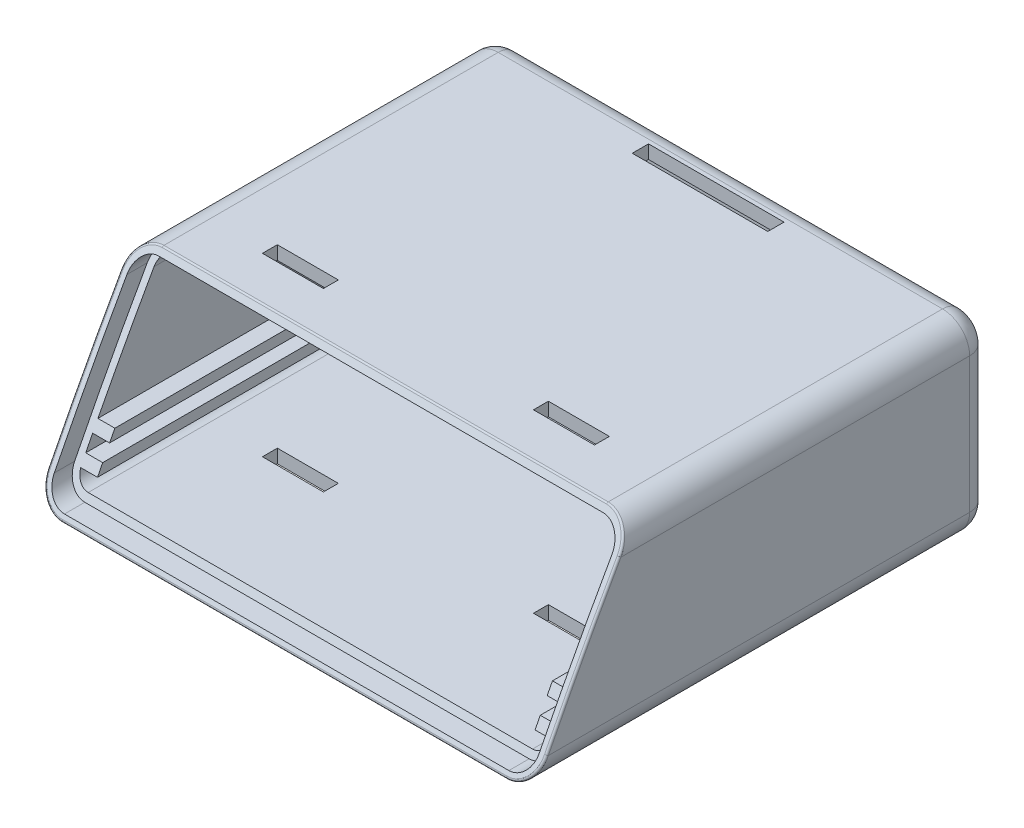
SolidWorks part; units mm, degrees
ref_plane "Front Plane" through (0, 0, 0) normal (0, 0, 1) x (1, 0, 0)
ref_plane "Top Plane" through (0, 0, 0) normal (0, 1, 0) x (1, 0, 0)
ref_plane "Right Plane" through (0, 0, 0) normal (1, 0, 0) x (0, 0, -1)
sketch "Sketch1" plane through (0, 0, 0) normal (0, 1, 0) x (1, 0, 0)
  line L1 (-36.79, -33.75) -> (36.79, -33.75)
  line L2 (-36.79, -33.75) -> (-36.79, 33.75)
  line L3 (-36.79, 33.75) -> (36.79, 33.75)
  line L4 (36.79, -33.75) -> (36.79, 33.75)
  line L5 (-36.79, -33.75) -> (36.79, 33.75) construction
  line L6 (-36.79, 33.75) -> (36.79, -33.75) construction
  point P0 (0, 0)
  dimension "D1" = 67.5
  dimension "D2" = 73.58
extrude "Boss-Extrude1" add sketch "Sketch1" along normal blind 28
fillet "Fillet1" radius 4 4 edges at (36.79, 28, 0) (36.79, 0, 0) (-36.79, 0, 0) (-36.79, 28, 0)
shell "Shell1" thickness 2
sketch "Sketch2" plane through (-36.79, 0, 0) normal (-1, 0, 0) x (0, 0, 1)
  line L0 (-33.75, 28) -> (33.75, 28) construction
  line L1 (18.75, 28) -> (33.75, 28)
  line L2 (33.75, 28) -> (33.75, 0)
  arc A0 (33.75, 0) -> (18.75, 28) centre (-392.2189, -210.1797) ccw
  dimension "D1" = 15
  dimension "D2" = 475
extrude "Cut-Extrude1" cut sketch "Sketch2" against normal through all
sketch "Sketch3" plane through (0, 0, -33.75) normal (0, 0, -1) x (-1, 0, 0)
  line L0 (-7.15, 18.7) -> (7.15, 18.7)
  line L1 (-6.95, 18.5) -> (6.95, 18.5) construction
  line L2 (-6.95, 18.5) -> (-6.95, 2.2) construction
  line L3 (-6.95, 2.2) -> (6.95, 2.2) construction
  line L4 (6.95, 18.5) -> (6.95, 2.2) construction
  line L5 (7.15, 18.7) -> (7.15, 2)
  line L6 (-7.15, 2) -> (7.15, 2)
  line L7 (-7.15, 18.7) -> (-7.15, 2)
  line L8 (27.25, 17.2) -> (38.3, 17.2)
  line L9 (27.45, 17) -> (38.1, 17) construction
  line L10 (27.45, 17) -> (27.45, 3.35) construction
  line L11 (27.45, 3.35) -> (38.1, 3.35) construction
  line L12 (38.1, 17) -> (38.1, 3.35) construction
  line L13 (38.3, 17.2) -> (38.3, 3.15)
  line L14 (27.25, 3.15) -> (38.3, 3.15)
  line L15 (27.25, 17.2) -> (27.25, 3.15)
  dimension "D1" = 0.2
  dimension "D2" = 0.2
fillet "Fillet2" radius 3 8 edges at (35.6184, 26.8284, -33.75) (36.79, 14, -33.75) (35.6184, 1.1716, -33.75) (0, 0, -33.75) (-35.6184, 1.1716, -33.75) (-36.79, 14, -33.75) (-35.6184, 26.8284, -33.75) (0, 28, -33.75)
sketch "Sketch4" plane through (0, 0, -31.75) normal (0, 0, 1) x (1, 0, 0)
  line L0 (32.79, 27) -> (-32.79, 27)
  line L1 (-35.79, 24) -> (-35.79, 4)
  line L2 (-32.79, 1) -> (32.79, 1)
  line L3 (35.79, 4) -> (35.79, 24)
  line L4 (32.79, 26) -> (-32.79, 26)
  line L5 (-34.79, 24) -> (-34.79, 4)
  line L6 (-32.79, 2) -> (32.79, 2)
  line L7 (34.79, 4) -> (34.79, 24)
  line L8 (32.79, 26) -> (-32.79, 26)
  line L9 (-34.79, 24) -> (-34.79, 4)
  line L10 (-32.79, 2) -> (32.79, 2)
  line L11 (34.79, 4) -> (34.79, 24)
  arc A0 (-32.79, 27) -> (-35.79, 24) centre (-32.79, 24) ccw
  arc A1 (-35.79, 4) -> (-32.79, 1) centre (-32.79, 4) ccw
  arc A2 (32.79, 1) -> (35.79, 4) centre (32.79, 4) ccw
  arc A3 (35.79, 24) -> (32.79, 27) centre (32.79, 24) ccw
  arc A4 (-32.79, 26) -> (-34.79, 24) centre (-32.79, 24) ccw
  arc A5 (-34.79, 4) -> (-32.79, 2) centre (-32.79, 4) ccw
  arc A6 (32.79, 2) -> (34.79, 4) centre (32.79, 4) ccw
  arc A7 (34.79, 24) -> (32.79, 26) centre (32.79, 24) ccw
  arc A8 (-32.79, 26) -> (-34.79, 24) centre (-32.79, 24) ccw
  arc A9 (-34.79, 4) -> (-32.79, 2) centre (-32.79, 4) ccw
  arc A10 (32.79, 2) -> (34.79, 4) centre (32.79, 4) ccw
  arc A11 (34.79, 24) -> (32.79, 26) centre (32.79, 24) ccw
  dimension "D1" = 0
  dimension "D2" = 1
extrude "Cut-Extrude3" cut sketch "Sketch4" against normal offset from surface (19.4971 mm away) 3 from offset 80
fillet "Fillet3" radius 0.3 8 edges at (35.4342, 27.0013, 19.3272) (36.79, 14.064, 26.517) (35.0952, 0.7311, 33.3885) (0, 0, 33.75) (-35.7081, 1.2642, 33.1239) (-36.79, 14.064, 26.517) (-35.0392, 27.3077, 19.1504) (0, 28, 18.75)
sketch "Sketch5" plane through (0, 0, -31.75) normal (0, 0, 1) x (1, 0, 0)
  line L1 (34.79, 5.25) -> (32.29, 5.25)
  line L2 (34.79, 5.25) -> (34.79, 3.75)
  line L3 (34.79, 3.75) -> (32.29, 3.75)
  line L4 (32.29, 5.25) -> (32.29, 3.75)
  line L5 (34.79, 7.05) -> (40.64, 7.05) construction
  line L6 (34.79, 7.25) -> (32.29, 7.25)
  line L7 (34.79, 7.25) -> (34.79, 8.75)
  line L8 (34.79, 8.75) -> (32.29, 8.75)
  line L9 (32.29, 7.25) -> (32.29, 8.75)
  line L10 (-40.64, 7.05) -> (40.64, 7.05) construction
  line L11 (40.64, 5.45) -> (34.79, 5.45) construction
  line L12 (-40.64, 5.45) -> (40.64, 5.45) construction
  line L14 (-34.79, 8.75) -> (-32.29, 8.75)
  line L15 (-34.79, 8.75) -> (-34.79, 7.25)
  line L16 (-34.79, 7.25) -> (-32.29, 7.25)
  line L17 (-32.29, 8.75) -> (-32.29, 7.25)
  line L18 (-34.79, 24) -> (-34.79, 4) construction
  line L19 (-34.79, 5.25) -> (-32.29, 5.25)
  line L20 (-34.79, 5.25) -> (-34.79, 3.75)
  line L21 (-34.79, 3.75) -> (-32.29, 3.75)
  line L22 (-32.29, 5.25) -> (-32.29, 3.75)
  line L23 (34.79, 24) -> (34.79, 4) construction
  dimension "D1" = 0.2
  dimension "D2" = 0.2
  dimension "D3" = 1.5
  dimension "D4" = 2.5
extrude "Boss-Extrude2" add sketch "Sketch5" along normal up to surface (59.8691 mm away)
sketch "Sketch6" plane through (0, 0, -33.75) normal (0, 0, -1) x (-1, 0, 0)
  line L0 (-7.15, 18.7) -> (7.15, 18.7)
  line L1 (-6.95, 18.5) -> (6.95, 18.5) construction
  line L2 (-6.95, 18.5) -> (-6.95, 2.2) construction
  line L3 (-6.95, 2.2) -> (6.95, 2.2) construction
  line L4 (6.95, 18.5) -> (6.95, 2.2) construction
  line L5 (7.15, 18.7) -> (7.15, 2)
  line L6 (-7.15, 2) -> (7.15, 2)
  line L7 (-7.15, 18.7) -> (-7.15, 2)
  line L8 (20.9, 17.2) -> (31.95, 17.2)
  line L9 (21.1, 17) -> (31.75, 17) construction
  line L10 (21.1, 17) -> (21.1, 3.35) construction
  line L11 (21.1, 3.35) -> (31.75, 3.35) construction
  line L12 (31.75, 17) -> (31.75, 3.35) construction
  line L13 (31.95, 17.2) -> (31.95, 3.15)
  line L14 (20.9, 3.15) -> (31.95, 3.15)
  line L15 (20.9, 17.2) -> (20.9, 3.15)
  dimension "D1" = 0.2
  dimension "D2" = 0.2
extrude "Cut-Extrude4" cut sketch "Sketch6" against normal up to surface (2 mm away) up to face at (0, 9.2763, -31.75)
sketch "Sketch7" plane through (0, 28, 0) normal (0, 1, 0) x (1, 0, 0)
  line L0 (0, 0) -> (0, 30.75) construction
  line L1 (23.5, -12.13) -> (16.5, -12.13) construction
  line L2 (23.5, -12.13) -> (23.5, -10.33) construction
  line L3 (23.5, -10.33) -> (16.5, -10.33) construction
  line L4 (16.5, -12.13) -> (16.5, -10.33) construction
  line L5 (15.5, -10.13) -> (24.5, -10.13)
  line L6 (15.5, -10.13) -> (15.5, -12.33)
  line L7 (15.5, -12.33) -> (24.5, -12.33)
  line L8 (24.5, -10.13) -> (24.5, -12.33)
  line L9 (32.79, 30.75) -> (-32.79, 30.75) construction
  line L10 (-16.5, -12.13) -> (-16.5, -10.33) construction
  line L11 (-23.5, -10.33) -> (-16.5, -10.33) construction
  line L12 (-23.5, -12.13) -> (-23.5, -10.33) construction
  line L13 (-23.5, -12.13) -> (-16.5, -12.13) construction
  line L14 (-24.5, -10.13) -> (-24.5, -12.33)
  line L15 (-15.5, -12.33) -> (-24.5, -12.33)
  line L16 (-15.5, -10.13) -> (-15.5, -12.33)
  line L17 (-15.5, -10.13) -> (-24.5, -10.13)
  dimension "D1" = 0.2
  dimension "D2" = 0.2
  dimension "D3" = 1
  dimension "D4" = 1
extrude "Cut-Extrude5" cut sketch "Sketch7" against normal through all
sketch "Sketch8" plane through (0, 28, 0) normal (0, 1, 0) x (1, 0, 0)
  line L0 (-32.79, 33.75) -> (32.79, 33.75) construction
  line L1 (-10, 30.15) -> (10, 30.15)
  line L2 (-10, 30.15) -> (-10, 27.75)
  line L3 (-10, 27.75) -> (10, 27.75)
  line L4 (10, 30.15) -> (10, 27.75)
  line L5 (0, 0) -> (0, 27.75) construction
  dimension "D1" = 3.6
  dimension "D2" = 2.4
  dimension "D3" = 20
extrude "Cut-Extrude6" cut sketch "Sketch8" against normal up to surface (2 mm away) up to face at (-20, 26, 11.23)
